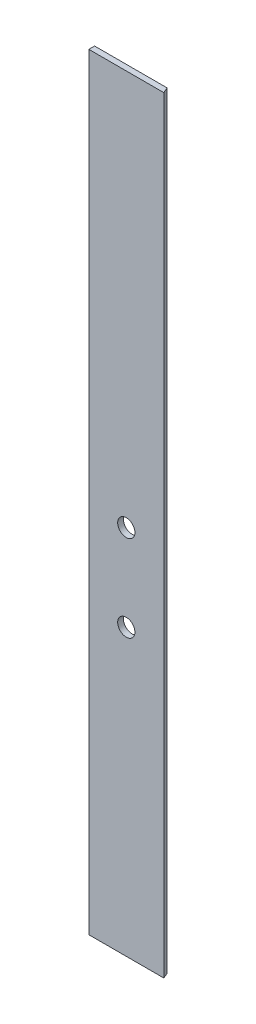
SolidWorks part; units mm, degrees
ref_plane "Спереди" through (0, 0, 0) normal (0, 0, 1) x (1, 0, 0)
ref_plane "Сверху" through (0, 0, 0) normal (0, 1, 0) x (1, 0, 0)
ref_plane "Справа" through (0, 0, 0) normal (1, 0, 0) x (0, 0, -1)
sketch "Эскиз1" plane through (0, 0, 0) normal (0, 1, 0) x (1, 0, 0)
  line L1 (0, -1) -> (50.4852, -1)
  line L2 (0, -1) -> (0, -5)
  line L3 (0, -5) -> (52.1029, -5)
  line L4 (50.4852, -1) -> (52.1029, -5)
  dimension "D1" = 4
extrude "Вытянуть1" add sketch "Эскиз1" along normal blind 533.2
sketch "Sketch1" plane through (0, 0, 5) normal (0, 0, 1) x (1, 0, 0)
  line L0 (26.0514, 28.9644) -> (26.0514, -44.8536) construction
  line L2 (0, 533.2) -> (52.1029, 533.2) construction
  circle A0 centre (26.0514, 258.2) radius 6
  circle A1 centre (26.0514, 198.2) radius 6
  dimension "D1" = 275
  dimension "D2" = 335
extrude "Cut-Extrude1" cut sketch "Sketch1" against normal through all
